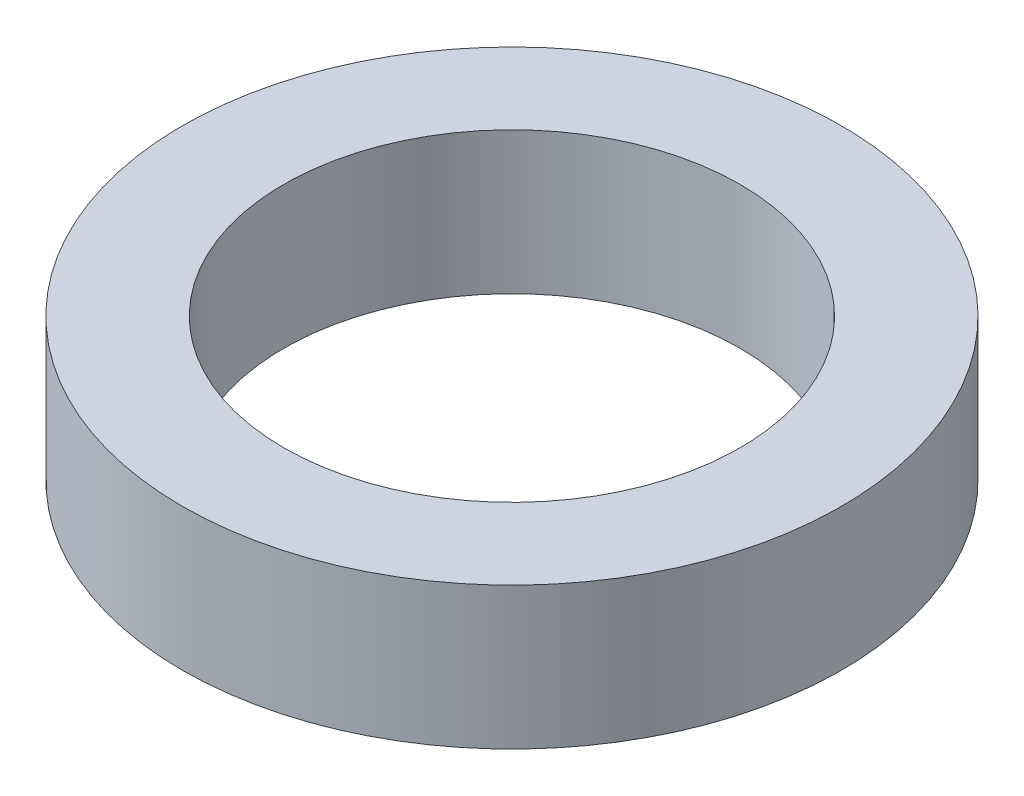
SolidWorks part; units mm, degrees
ref_plane "Front Plane" through (0, 0, 0) normal (0, 0, 1) x (1, 0, 0)
ref_plane "Top Plane" through (0, 0, 0) normal (0, 1, 0) x (1, 0, 0)
ref_plane "Right Plane" through (0, 0, 0) normal (1, 0, 0) x (0, 0, -1)
sketch "Sketch1" plane through (0, 0, 0) normal (0, 1, 0) x (1, 0, 0)
  circle A0 centre (0, 0) radius 65
  dimension "FLANGE_OD" = 130
extrude "Boss-Extrude1" add sketch "Sketch1" along normal blind 28
sketch "Sketch2" plane through (0, 0, 0) normal (0, 1, 0) x (1, 0, 0)
  circle A0 centre (0, 0) radius 45
  dimension "BORE_D" = 90
extrude "Cut-Extrude1" cut sketch "Sketch2" along normal through all
sketch "Sketch3" plane through (0, 28, 0) normal (0, 1, 0) x (1, 0, 0)
  circle A0 centre (0, 0) radius 26.1763 construction
  circle A1 centre (-26.1763, 0) radius 2.3282
  dimension "BOLT_D" = 4.6563
  dimension "BOLT_PCD" = 52.3525
extrude "Cut-Extrude2" cut sketch "Sketch3" against normal blind 26.5851 rebuild error yes
pattern_circular "CirPattern1" count 3 over 360 rebuild error yes
